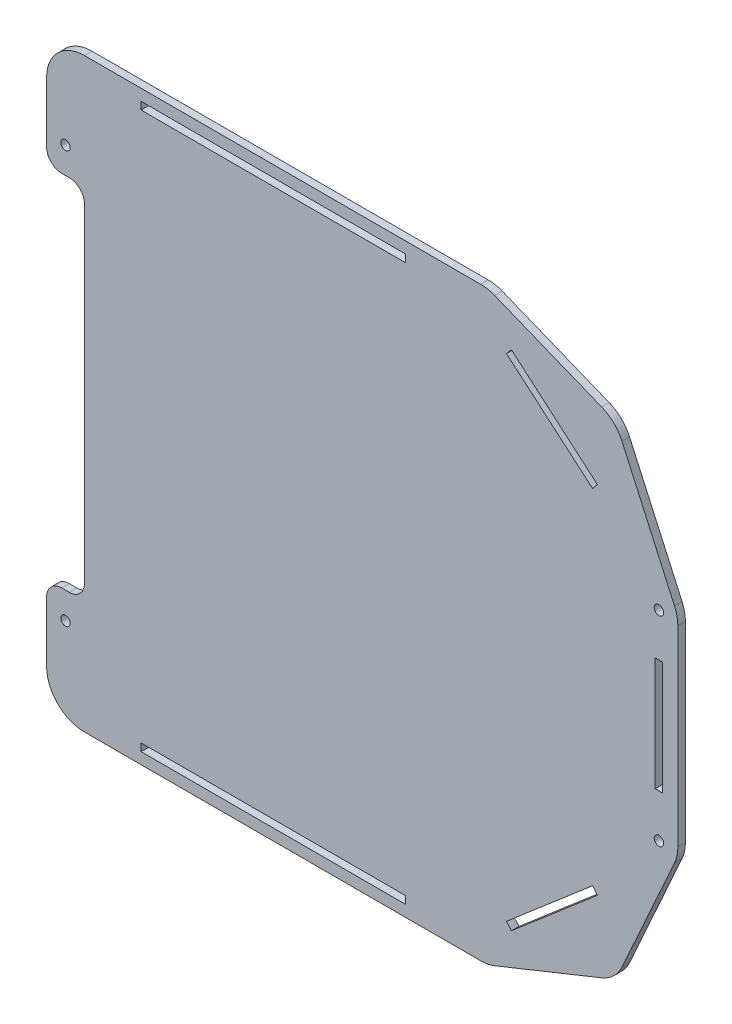
SolidWorks part; units mm, degrees
material "PVC rigido"
ref_plane "Piano frontale" through (0, 0, 0) normal (0, 0, 1) x (1, 0, 0)
ref_plane "Piano superiore" through (0, 0, 0) normal (0, 1, 0) x (1, 0, 0)
ref_plane "Piano destro" through (0, 0, 0) normal (1, 0, 0) x (0, 0, -1)
sketch "Schizzo1" plane through (0, 0, 0) normal (0, 0, 1) x (1, 0, 0)
  line L0 (25.7647, -77.5) -> (59.5674, -63.9093)
  line L1 (-91, -77.5) -> (25.7647, -77.5)
  line L2 (-91, -77.5) -> (-91, 77.5)
  line L3 (-91, 77.5) -> (25.7647, 77.5)
  line L4 (76, -27.5) -> (76, 27.5)
  line L5 (69.2392, 67.1366) -> (85.1147, 31.9616) construction
  line L6 (59.5674, -63.9093) -> (59.5674, 63.9093) construction
  line L7 (59.5674, -63.9093) -> (76, -27.5)
  line L8 (25.7647, 77.5) -> (59.5674, 63.9093)
  line L9 (59.5674, 63.9093) -> (76, 27.5)
  line L10 (25.7647, 77.5) -> (76, 77.5) construction
  line L11 (76, 77.5) -> (76, 27.5) construction
  line L12 (25.7647, -77.5) -> (76, -77.5) construction
  line L13 (76, -77.5) -> (76, -27.5) construction
  line L14 (63.8549, -72.3011) -> (27.8474, -86.7782) construction
  line L15 (85.1147, -31.9616) -> (69.2392, -67.1366) construction
  line L16 (27.8474, 86.7782) -> (63.8549, 72.3011) construction
  line L17 (0, 0) -> (25.7647, 77.5) construction
  line L18 (0, 0) -> (25.7647, -77.5) construction
  line L19 (25.7647, -77.5) -> (25.7647, 77.5) construction
  line L20 (-91, -77.5) -> (0, 0) construction
  line L21 (0, 0) -> (-91, 77.5) construction
  line L22 (0, 0) -> (-91, 0) construction
  line L23 (0, 0) -> (0, 77.5) construction
  line L24 (86, 27.8479) -> (86, -27.8479) construction
  point P0 (0, 0)
  dimension "D1" = 155
  dimension "D2" = 91
  dimension "D3" = 55
  dimension "D4" = 10
extrude "Estrusione-Estrusione1" add sketch "Schizzo1" along normal blind 2
hole_wizard "Foro filettato M3x0.5-1" positions "Schizzo3" profile "Schizzo2" tap size "M3x0.5" standard "Ansi Metric" end condition through all
sketch "Schizzo3" plane through (0, 0, 0) normal (0, 0, -1) x (-1, 0, 0)
  line L0 (86, -77.5) -> (86, -54.5) construction
  line L1 (91, -77.5) -> (-25.7647, -77.5) construction
  line L2 (86, -54.5) -> (86, 54.5) construction
  line L3 (86, 54.5) -> (86, 77.5) construction
  line L4 (-25.7647, 77.5) -> (91, 77.5) construction
  line L6 (0, 0) -> (86, 0) construction
  point P0 (86, -54.5)
  point P2 (86, 54.5)
sketch "Schizzo2" plane through (-86, -54.5, 0) normal (1, 0, 0) x (0, 1, 0)
  line L0 (0, 0) -> (0, 2)
  line L1 (0, 2) -> (1.25, 2)
  line L2 (1.25, 2) -> (1.25, 0)
  line L5 (1.25, 0) -> (0, 0)
  line L11 (0, -6.35) -> (0, 107.95) construction
  dimension "Thru Tap Drill Dia." = 2.5
  dimension "Thru Tap Drill Depth" = 2
cosmetic thread "Filettatura del foro1" parameters "D2"=3
cosmetic thread "Filettatura del foro2" parameters "D2"=3
sketch "Schizzo4" plane through (0, 0, 0) normal (0, 0, -1) x (-1, 0, 0)
  line L0 (31, -72.5) -> (31, 72.5) construction
  line L1 (66, -74.5) -> (-4, -74.5)
  line L2 (66, -74.5) -> (66, -72.5)
  line L3 (66, -72.5) -> (-4, -72.5)
  line L4 (-4, -74.5) -> (-4, -72.5)
  line L5 (66, 72.5) -> (-4, 72.5)
  line L6 (66, 72.5) -> (66, 74.5)
  line L7 (66, 74.5) -> (-4, 74.5)
  line L8 (-4, 72.5) -> (-4, 74.5)
  line L9 (31, 0) -> (91, 0) construction
  line L10 (91, 77.5) -> (91, -77.5) construction
  line L11 (91, -77.5) -> (-25.7647, -77.5) construction
  dimension "D1" = 2
  dimension "D2" = 3
  dimension "D3" = 70
  dimension "D4" = 60
extrude "Taglio-Estrusione1" cut sketch "Schizzo4" against normal blind 10
hole_wizard "Foro filettato M3x0.5-2" positions "Schizzo6" profile "Schizzo5" tap size "M3x0.5" standard "Ansi Metric" end condition through all
sketch "Schizzo6" plane through (0, 0, 2) normal (0, 0, 1) x (1, 0, 0)
  line L16 (55.0101, -61.8525) -> (71, -26.4239)
  line L17 (71, -26.4239) -> (71, 26.4239)
  line L18 (71, 26.4239) -> (55.0101, 61.8525)
  line L19 (55.0101, -61.8525) -> (71, -26.4239) construction
  line L20 (71, -26.4239) -> (71, 26.4239) construction
  line L21 (71, 26.4239) -> (55.0101, 61.8525) construction
  point P0 (71, 26.4239)
  point P2 (71, -26.4239)
  dimension "D1" = 5
sketch "Schizzo5" plane through (71, 26.4239, 2) normal (1, 0, 0) x (0, -1, 0)
  line L0 (0, 0) -> (0, 2)
  line L1 (0, 2) -> (1.25, 2)
  line L2 (1.25, 2) -> (1.25, 0)
  line L5 (1.25, 0) -> (0, 0)
  line L11 (0, -6.35) -> (0, 107.95) construction
  dimension "Thru Tap Drill Dia." = 2.5
  dimension "Thru Tap Drill Depth" = 2
cosmetic thread "Filettatura del foro3" parameters "D2"=3
cosmetic thread "Filettatura del foro4" parameters "D2"=3
sketch "Schizzo7" plane through (0, 0, 2) normal (0, 0, 1) x (1, 0, 0)
  line L0 (31.9679, 66.557) -> (54.746, 47.0338)
  line L1 (53.4445, 45.5153) -> (30.6663, 65.0385)
  line L2 (30.6663, 65.0385) -> (31.9679, 66.557)
  line L3 (53.4445, 45.5153) -> (54.746, 47.0338)
  line L4 (71, 26.4239) -> (4, 73.5) construction
  line L5 (4, 74.5) -> (4, 72.5) construction
  line L6 (4, 74.5) -> (4, 72.5) construction
  line L7 (31.3171, 65.7977) -> (54.0953, 46.2746) construction
  line L8 (42.7062, 56.0361) -> (37.5, 49.962) construction
  line L9 (71, 26.4239) -> (71, 15) construction
  line L10 (71, 15) -> (71, -15) construction
  line L11 (71, -15) -> (71, -26.4239) construction
  line L12 (71, -26.4239) -> (4, -73.5) construction
  line L13 (59.5674, -63.9093) -> (42.7062, -56.0361) construction
  line L14 (54.0953, -46.2746) -> (76, -27.5) construction
  line L15 (4, -72.5) -> (4, -74.5) construction
  line L16 (53.4445, -45.5153) -> (30.6663, -65.0385)
  line L17 (30.6663, -65.0385) -> (31.9679, -66.557)
  line L18 (31.9679, -66.557) -> (54.746, -47.0338)
  line L19 (54.746, -47.0338) -> (53.4445, -45.5153)
  line L20 (54.0953, -46.2746) -> (31.3171, -65.7977) construction
  line L21 (37.5, -49.962) -> (42.7062, -56.0361) construction
  line L22 (76, 27.5) -> (54.0953, 46.2746) construction
  line L23 (72, -15) -> (70, -15)
  line L24 (72, -15) -> (72, 15)
  line L25 (72, 15) -> (70, 15)
  line L26 (70, -15) -> (70, 15)
  dimension "D1" = 30
  dimension "D2" = 8
  dimension "D3" = 30
extrude "Taglio-Estrusione2" cut sketch "Schizzo7" against normal blind 10
sketch "Schizzo8" plane through (0, 0, 2) normal (0, 0, 1) x (1, 0, 0)
  line L0 (-91, 77.5) -> (-91, -77.5) construction
  line L1 (-91, -47.5) -> (-81, -47.5)
  line L2 (-91, -47.5) -> (-91, 47.5)
  line L3 (-91, 47.5) -> (-81, 47.5)
  line L4 (-81, -47.5) -> (-81, 47.5)
  line L5 (-86, -54.5) -> (-86, -47.5) construction
  line L6 (-86, 54.5) -> (-86, 47.5) construction
  dimension "D1" = 95
extrude "Taglio-Estrusione3" cut sketch "Schizzo8" against normal blind 10
fillet "Raccordo1" radius 10 2 edges at (-91, 77.5, 1) (-91, -77.5, 1)
fillet "Raccordo2" radius 10 6 edges at (25.7647, -77.5, 1) (59.5674, -63.9093, 1) (76, -27.5, 1) (76, 27.5, 1) (59.5674, 63.9093, 1) (25.7647, 77.5, 1)
fillet "Raccordo3" radius 4 4 edges at (-81, 47.5, 1) (-91, 47.5, 1) (-81, -47.5, 1) (-91, -47.5, 1)
sketch "Schizzo9" plane through (0, 0, 2) normal (0, 0, 1) x (1, 0, 0)
  line L0 (-2.0763, 31.6435) -> (-2.0763, -8.3551)
  line L1 (-22.0756, 11.6442) -> (17.923, 11.6442)
  line L2 (-2.0763, 11.6442) -> (-2.7758, 15.5826) construction
  line L3 (-2.7758, 15.5826) -> (-4.1747, 23.4586) construction
  line L4 (-4.1747, 23.4586) -> (-5.5735, 31.3347) construction
  line L5 (-15.0728, -3.5566) -> (10.9201, 26.845)
  line L6 (10.2297, -4.1208) -> (-14.3823, 27.4092)
  circle A0 centre (-2.0763, 11.6442) radius 19.9993
  circle A1 centre (-2.0763, 11.6442) radius 11.9993
  circle A2 centre (-2.0763, 11.6442) radius 4
  point P9 (-2.0763, 11.6442)
  dimension "D1" = 8
  dimension "D2" = 8
other "Ventola1" [suppressed] parameters "RibsDepth"=1, "RibsWidth"=5, "RibsOffset"=0, "SparsDepth"=1, "SparsWidth"=2, "SparsOffset"=0, "SupportDepth"=1, "SupportOffset"=0, "Draft"=1
